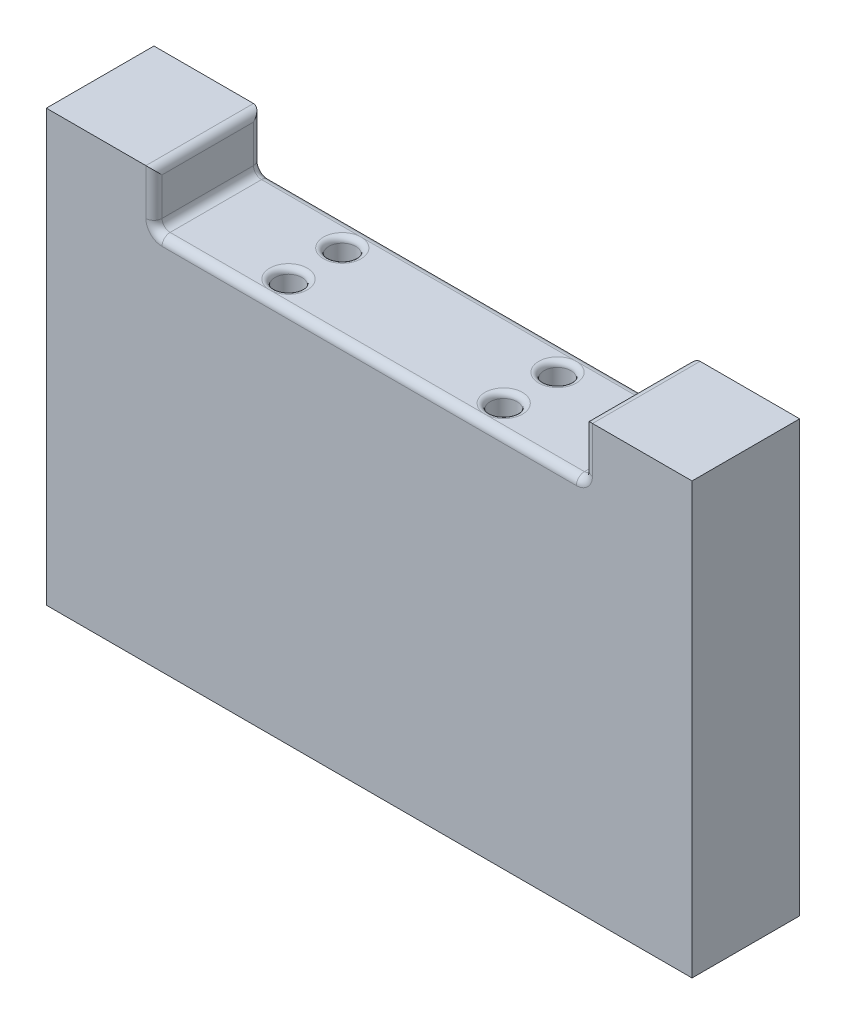
SolidWorks part; units mm, degrees
material "6061-T6 (SS)"
ref_plane "Front Plane" through (0, 0, 0) normal (0, 0, 1) x (1, 0, 0)
ref_plane "Top Plane" through (0, 0, 0) normal (0, 1, 0) x (1, 0, 0)
ref_plane "Right Plane" through (0, 0, 0) normal (1, 0, 0) x (0, 0, -1)
sketch "Sketch2" plane through (0, 0, 0) normal (0, 0, 1) x (1, 0, 0)
  line L1 (-60, -40) -> (60, -40)
  line L2 (-60, -40) -> (-60, 40)
  line L3 (-60, 40) -> (60, 40)
  line L4 (60, -40) -> (60, 40)
  line L5 (-60, -40) -> (60, 40) construction
  line L6 (-60, 40) -> (60, -40) construction
  point P0 (0, 0)
  dimension "D1" = 120
  dimension "D2" = 80
extrude "Boss-Extrude1" add sketch "Sketch2" along normal blind 20
sketch "Sketch3" plane through (0, 40, 0) normal (0, 1, 0) x (1, 0, 0)
  line L1 (-40, 20) -> (40, 20)
  line L2 (-40, 20) -> (-40, -20)
  line L3 (-40, -20) -> (40, -20)
  line L4 (40, 20) -> (40, -20)
  line L5 (-40, 20) -> (40, -20) construction
  line L6 (-40, -20) -> (40, 20) construction
  point P0 (0, 0)
  dimension "D1" = 80
  dimension "D2" = 40
extrude "Cut-Extrude1" cut sketch "Sketch3" against normal blind 10
sketch "Sketch5" plane through (0, 30, 0) normal (0, 1, 0) x (1, 0, 0)
  line L0 (-40, 0) -> (-40, -20) construction
  line L1 (40, -20) -> (40, 0) construction
  line L2 (-40, -20) -> (40, -20) construction
  line L3 (-40, 0) -> (40, 0) construction
  circle A0 centre (-20, -5) radius 2.5
  circle A1 centre (-20, -15) radius 2.5
  circle A2 centre (20, -5) radius 2.5
  circle A3 centre (20, -15) radius 2.5
  dimension "D1" = 5
  dimension "D2" = 5
  dimension "D3" = 5
  dimension "D4" = 5
  dimension "D5" = 20
  dimension "D6" = 20
  dimension "D7" = 20
  dimension "D8" = 20
  dimension "D9" = 5
  dimension "D10" = 5
  dimension "D11" = 5
  dimension "D12" = 5
extrude "Cut-Extrude3" cut sketch "Sketch5" against normal through all
fillet "Fillet5" radius 1 8 edges at (20, 30, 17.5) (20, -40, 17.5) (20, 30, 7.5) (20, -40, 7.5) (-20, 30, 17.5) (-20, -40, 17.5) (-20, 30, 7.5) (-20, -40, 7.5)
fillet "Fillet6" radius 1.5 10 edges at (0, 30, 0) (0, 30, 20) (40, 40, 10) (40, 35, 20) (40, 30, 10) (40, 35, 0) (-40, 30, 10) (-40, 35, 20) (-40, 40, 10) (-40, 35, 0)
